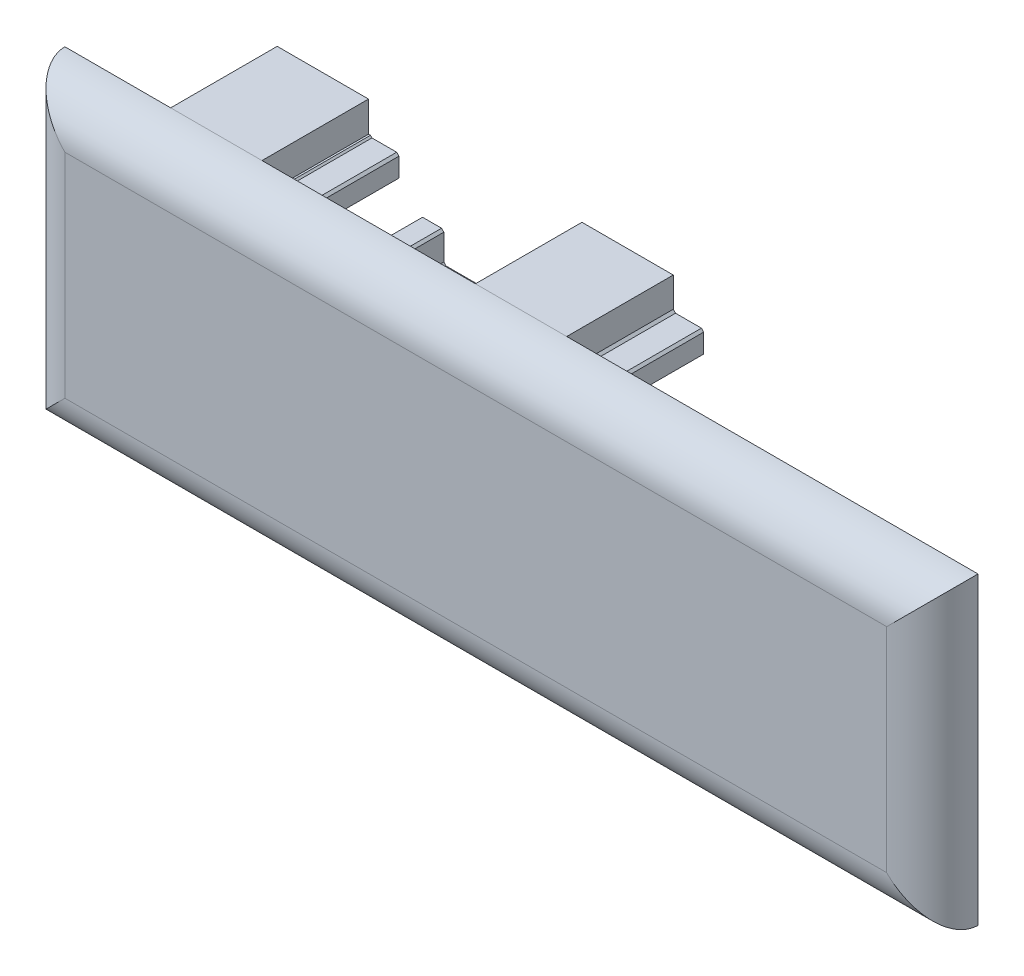
SolidWorks part; units mm, degrees
ref_plane "前视基准面" through (0, 0, 0) normal (0, 0, 1) x (1, 0, 0)
ref_plane "上视基准面" through (0, 0, 0) normal (0, 1, 0) x (1, 0, 0)
ref_plane "右视基准面" through (0, 0, 0) normal (1, 0, 0) x (0, 0, -1)
sketch "草图1" plane through (0, 0, 0) normal (0, 0, 1) x (1, 0, 0)
  line L0 (0, -1000) -> (0, 49000) construction
  line L1 (-3.2, 10) -> (-3.2, 8.5) construction
  line L2 (-10, -10) -> (10, -10) construction
  line L3 (-10, -10) -> (-10, 10) construction
  line L4 (-10, 10) -> (10, 10) construction
  line L5 (-1000, 0) -> (49000, 0) construction
  line L6 (10, -10) -> (10, 10) construction
  line L7 (-10, -10) -> (10, 10) construction
  line L8 (-10, 10) -> (10, -10) construction
  line L9 (-3.2, 8.5) -> (-5.5, 8.5) construction
  line L10 (-5.5, 8.5) -> (-5.5, 6.7) construction
  line L11 (-5.5, 6.7) -> (-2.8, 4) construction
  line L12 (-2.8, 4) -> (2.8, 4) construction
  line L13 (5.5, 6.7) -> (2.8, 4) construction
  line L14 (5.5, 8.5) -> (5.5, 6.7) construction
  line L15 (3.2, 8.5) -> (5.5, 8.5) construction
  line L16 (3.2, 10) -> (3.2, 8.5) construction
  line L17 (8.5, 3.2) -> (8.5, 5.5) construction
  line L18 (8.5, 5.5) -> (6.7, 5.5) construction
  line L19 (6.7, 5.5) -> (4, 2.8) construction
  line L20 (4, 2.8) -> (4, -2.8) construction
  line L21 (6.7, -5.5) -> (4, -2.8) construction
  line L22 (8.5, -5.5) -> (6.7, -5.5) construction
  line L23 (8.5, -3.2) -> (8.5, -5.5) construction
  line L24 (10, 3.2) -> (8.5, 3.2) construction
  line L25 (10, -3.2) -> (8.5, -3.2) construction
  line L26 (3.2, -8.5) -> (5.5, -8.5) construction
  line L27 (5.5, -8.5) -> (5.5, -6.7) construction
  line L28 (5.5, -6.7) -> (2.8, -4) construction
  line L29 (2.8, -4) -> (-2.8, -4) construction
  line L30 (-5.5, -6.7) -> (-2.8, -4) construction
  line L31 (-5.5, -8.5) -> (-5.5, -6.7) construction
  line L32 (-3.2, -8.5) -> (-5.5, -8.5) construction
  line L33 (3.2, -10) -> (3.2, -8.5) construction
  line L34 (-3.2, -10) -> (-3.2, -8.5) construction
  line L35 (-8.5, -3.2) -> (-8.5, -5.5) construction
  line L36 (-8.5, -5.5) -> (-6.7, -5.5) construction
  line L37 (-6.7, -5.5) -> (-4, -2.8) construction
  line L38 (-4, -2.8) -> (-4, 2.8) construction
  line L39 (-6.7, 5.5) -> (-4, 2.8) construction
  line L40 (-8.5, 5.5) -> (-6.7, 5.5) construction
  line L41 (-8.5, 3.2) -> (-8.5, 5.5) construction
  line L42 (-10, -3.2) -> (-8.5, -3.2) construction
  line L43 (-10, 3.2) -> (-8.5, 3.2) construction
  line L44 (-10, 10) -> (-50, 10) construction
  line L45 (-50, 10) -> (-50, -10) construction
  line L46 (-50, -10) -> (-10, -10) construction
  line L47 (-50, -10) -> (21, -10)
  line L48 (-21, 30) -> (21, 30) construction
  line L49 (-21, 30) -> (-21, 44.755)
  line L50 (-16, 72) -> (-6.245, 72)
  line L51 (21, 30) -> (21, 44.755)
  line L52 (-21, 30) -> (21, 72) construction
  line L53 (-21, 72) -> (21, 30) construction
  line L54 (161.103, 104.1617) -> (226.103, 104.1617) construction
  line L55 (161.103, 104.1617) -> (161.103, 51.1617) construction
  line L56 (161.103, 51.1617) -> (226.103, 51.1617) construction
  line L57 (226.103, 104.1617) -> (226.103, 51.1617) construction
  line L58 (21, -10) -> (21, 30)
  line L59 (-21, 13) -> (-50, 13)
  line L60 (-50, 10) -> (10, 10)
  line L61 (-21, 13) -> (-21, 30)
  line L62 (6.245, 72) -> (16, 72)
  line L63 (-21, 57.245) -> (-21, 67)
  line L64 (21, 57.245) -> (21, 67)
  line L65 (-21, 13) -> (10, 13)
  line L66 (10, 13) -> (10, 10)
  line L67 (-50, -10) -> (-50, 10)
  line L68 (-24.525, 6) -> (-15.525, 6)
  line L69 (-50, 13) -> (-50, 10)
  line L70 (-3, 10) -> (-3, 8)
  line L71 (-3, 8) -> (-5, 8)
  line L72 (-5, 8) -> (-5, 6.5)
  line L73 (-5, 6.5) -> (-4.5, 6)
  line L74 (-4.5, 6) -> (4.5, 6)
  line L75 (5, 6.5) -> (4.5, 6)
  line L76 (5, 8) -> (5, 6.5)
  line L77 (3, 10) -> (3, 8)
  line L78 (3, 8) -> (5, 8)
  line L79 (-15.025, 6.5) -> (-15.525, 6)
  line L80 (-15.025, 8) -> (-15.025, 6.5)
  line L81 (-17.025, 8) -> (-15.025, 8)
  line L82 (-17.025, 10) -> (-17.025, 8)
  line L83 (-23.025, 10) -> (-23.025, 8)
  line L84 (-23.025, 8) -> (-25.025, 8)
  line L85 (-25.025, 8) -> (-25.025, 6.5)
  line L86 (-25.025, 6.5) -> (-24.525, 6)
  line L87 (-44.55, 6) -> (-35.55, 6)
  line L88 (-35.05, 6.5) -> (-35.55, 6)
  line L89 (-35.05, 8) -> (-35.05, 6.5)
  line L90 (-37.05, 8) -> (-35.05, 8)
  line L91 (-37.05, 10) -> (-37.05, 8)
  line L92 (-43.05, 10) -> (-43.05, 8)
  line L93 (-43.05, 8) -> (-45.05, 8)
  line L94 (-45.05, 8) -> (-45.05, 6.5)
  line L95 (-45.05, 6.5) -> (-44.55, 6)
  line L96 (-30, 10) -> (-30, -10) construction
  line L97 (-40, 10) -> (-40, -10) construction
  line L98 (-34, 4.55) -> (-34, -4.45)
  line L99 (-33.5, -4.95) -> (-34, -4.45)
  line L100 (-32, -4.95) -> (-33.5, -4.95)
  line L101 (-32, -2.95) -> (-32, -4.95)
  line L102 (-32, 3.05) -> (-28, 3.05)
  line L103 (-28, -2.95) -> (-32, -2.95)
  line L104 (-32, 3.05) -> (-32, 5.05)
  line L105 (-32, 5.05) -> (-33.5, 5.05)
  line L106 (-33.5, 5.05) -> (-34, 4.55)
  line L107 (-35.45, -6) -> (-44.45, -6)
  line L108 (-44.95, -6.5) -> (-44.45, -6)
  line L109 (-44.95, -8) -> (-44.95, -6.5)
  line L110 (-42.95, -8) -> (-44.95, -8)
  line L111 (-42.95, -10) -> (-42.95, -8)
  line L112 (-36.95, -10) -> (-36.95, -8)
  line L113 (-36.95, -8) -> (-34.95, -8)
  line L114 (-34.95, -8) -> (-34.95, -6.5)
  line L115 (-34.95, -6.5) -> (-35.45, -6)
  line L116 (-46, -4.55) -> (-46, 4.45) construction
  line L117 (-46.5, 4.95) -> (-46, 4.45) construction
  line L118 (-48, 4.95) -> (-46.5, 4.95) construction
  line L119 (-48, 2.95) -> (-48, 4.95) construction
  line L120 (-50, 2.95) -> (-48, 2.95) construction
  line L121 (-50, -3.05) -> (-48, -3.05) construction
  line L122 (-48, -3.05) -> (-48, -5.05) construction
  line L123 (-48, -5.05) -> (-46.5, -5.05) construction
  line L124 (-46.5, -5.05) -> (-46, -4.55) construction
  line L125 (-26.5, 5.05) -> (-26, 4.55)
  line L126 (-28, 5.05) -> (-26.5, 5.05)
  line L127 (-28, 3.05) -> (-28, 5.05)
  line L128 (-28, -2.95) -> (-28, -4.95)
  line L129 (-28, -4.95) -> (-26.5, -4.95)
  line L130 (-26.5, -4.95) -> (-26, -4.45)
  line L131 (-26, 4.55) -> (-26, -4.45)
  line L132 (-30, -2.95) -> (-32, -2.95) [skipped]
  line L133 (-30, 3.05) -> (-32, 3.05) [skipped]
  line L134 (-25.025, -6.5) -> (-24.525, -6)
  line L135 (-25.025, -8) -> (-25.025, -6.5)
  line L136 (-23.025, -8) -> (-25.025, -8)
  line L137 (-23.025, -10) -> (-23.025, -8)
  line L138 (-17.025, -10) -> (-17.025, -8)
  line L139 (-17.025, -8) -> (-15.025, -8)
  line L140 (-15.025, -8) -> (-15.025, -6.5)
  line L141 (-15.025, -6.5) -> (-15.525, -6)
  line L142 (-24.525, -6) -> (-15.525, -6)
  line L143 (10, 10) -> (10, -10)
  circle A0 centre (0, 51) radius 11.5
  circle A1 centre (15.5, 66.5) radius 1.7
  circle A2 centre (15.5, 35.5) radius 1.7
  circle A3 centre (-15.5, 35.5) radius 1.7
  circle A4 centre (-15.5, 66.5) radius 1.7
  arc A5 (16, 72) -> (21, 67) centre (16, 67) cw
  arc A6 (-21, 67) -> (-16, 72) centre (-16, 67) cw
  arc A7 (-2.3419, 70.125) -> (2.3419, 70.125) centre (0, 72) ccw
  arc A8 (-2.3419, 70.125) -> (-6.245, 72) centre (-6.245, 67) ccw
  arc A9 (2.3419, 70.125) -> (6.245, 72) centre (6.245, 67) cw
  arc A10 (19.125, 53.3419) -> (19.125, 48.6581) centre (21, 51) ccw
  arc A11 (19.125, 48.6581) -> (21, 44.755) centre (16, 44.755) cw
  arc A12 (19.125, 53.3419) -> (21, 57.245) centre (16, 57.245) ccw
  arc A16 (-19.125, 48.6581) -> (-19.125, 53.3419) centre (-21, 51) ccw
  arc A17 (-19.125, 53.3419) -> (-21, 57.245) centre (-16, 57.245) cw
  arc A18 (-19.125, 48.6581) -> (-21, 44.755) centre (-16, 44.755) ccw
  point P0 (0, 0)
  point P18 (0, 4)
  point P23 (0, 51)
  point P58 (0, 0)
  point P82 (0, 51)
  point P93 (3, 72)
  point P110 (0, 6)
  point P118 (0, 51)
  point P154 (-40, 0)
  point P176 (-40, 0)
  point P188 (-40, 0)
  dimension "D12" = 3
  dimension "D17" = 3.4
  dimension "D20" = 5
  dimension "D21" = 3
  dimension "D22" = 5
  dimension "D23" = 5
  dimension "D1" = 20
  dimension "D2" = 20
  dimension "D3" = 6.4
  dimension "D4" = 1.5
  dimension "D5" = 11
  dimension "D6" = 6
  dimension "D7" = 1.8
  dimension "D9" = 60
  dimension "D10" = 42
  dimension "D11" = 42
  dimension "D13" = 20
  dimension "D14" = 53
  dimension "D15" = 65
  dimension "D16" = 3
  dimension "D19" = 31
  dimension "D26" = 3
  dimension "D27" = 2
  dimension "D28" = 2
  dimension "D29" = 1.5
  dimension "D30" = 2
  dimension "D31" = 4.5
  dimension "D33" = 10
  dimension "D8" = 10
  dimension "D18" = 4
extrude "凸台-拉伸1" add sketch "草图1" along normal blind 3 contours L143 L60 L77 L78 L76 L75 L74 L73 L72 L71 L70 L82 L81 L80 L79 L68 L86 L85 L84 L83 L91 L90 L89 L88 L87 L95 L94 L93 L92 L67 L47 L111 L110 L109 L108 L107 L115 L114 L113 L112 L137 L136 L135 L134 L142 L141 L140 | L85 L86 L68 L79 L80 L81 L82 L60 L83 L84 | L78 L77 L60 L70 L71 L72 L73 L74 L75 L76 | L131 L125 L126 L127 L102 L104 L105 L106 L98 L99 L100 L101 L103 L128 L129 L130 | L94 L95 L87 L88 L89 L90 L91 L60 L92 L93 | L114 L115 L107 L108 L109 L110 L111 L47 L112 L113 | L142 L134 L135 L136 L137 L47 L138 L139 L140 L141 region at (-18.6995, -0.2553, 0) region at (-39.95, -7.7625, 0) region at (-40.05, 7.7625, 0) region at (-20.025, -7.7625, 0) region at (-20.025, 7.7625, 0) region at (0, 7.7625, 0) region at (-30, 0.05, 0)
extrude "凸台-拉伸3" add sketch "草图1<5>" against normal blind 7 contours L85 L86 L68 L79 L80 L81 L82 L60 L83 L84 | L94 L95 L87 L88 L89 L90 L91 L60 L92 L93 | L131 L125 L126 L127 L102 L104 L105 L106 L98 L99 L100 L101 L103 L128 L129 L130 | L142 L134 L135 L136 L137 L47 L138 L139 L140 L141 | L114 L115 L107 L108 L109 L110 L111 L47 L112 L113 region at (-39.95, -7.7625, 0) region at (-40.05, 7.7625, 0) region at (-20.025, -7.7625, 0) region at (-20.025, 7.7625, 0) region at (-30, 0.05, 0)
sketch "草图1<5>" plane through (0, 0, 0) normal (0, 0, 1) x (1, 0, 0) same geometry as "草图1"
sketch "草图5" plane through (0, 0, -7) normal (0, 0, -1) x (-1, 0, 0)
  line L0 (17.025, 10) -> (17.025, 8) construction
  line L1 (15.025, 8) -> (17.025, 8)
  line L2 (15.025, 8) -> (15.025, 7.9)
  line L3 (15.025, 7.9) -> (17.025, 7.9)
  line L4 (17.025, 8) -> (17.025, 7.9)
  line L5 (-1000, 0) -> (49000, 0) construction
  line L6 (30, -996.95) -> (30, 49003.05) construction
  line L7 (32, 3.05) -> (28, 3.05) construction
  line L8 (20.025, -993.9) -> (20.025, 49006.1) construction
  line L9 (24.525, 6) -> (15.525, 6) construction
  line L10 (40.05, -993.9) -> (40.05, 49006.1) construction
  line L11 (44.55, 6) -> (35.55, 6) construction
  line L12 (23.025, 8) -> (23.025, 7.9)
  line L13 (25.025, 7.9) -> (23.025, 7.9)
  line L14 (25.025, 8) -> (25.025, 7.9)
  line L15 (25.025, 8) -> (23.025, 8)
  line L16 (34.975, 8) -> (36.975, 8)
  line L17 (34.975, 8) -> (34.975, 7.9)
  line L18 (34.975, 7.9) -> (36.975, 7.9)
  line L19 (36.975, 8) -> (36.975, 7.9)
  line L20 (42.975, 8) -> (42.975, 7.9)
  line L21 (44.975, 7.9) -> (42.975, 7.9)
  line L22 (44.975, 8) -> (44.975, 7.9)
  line L23 (44.975, 8) -> (42.975, 8)
  line L24 (28, 5.05) -> (26.5, 5.05) construction
  line L25 (27.9, 5.05) -> (32.1, 5.05)
  line L26 (27.9, 5.05) -> (27.9, 3.05)
  line L27 (27.9, 3.05) -> (32.1, 3.05)
  line L28 (32.1, 5.05) -> (32.1, 3.05)
  line L30 (32, 3.05) -> (32, 5.05) construction
  line L31 (32.1, -5.05) -> (32.1, -3.05)
  line L32 (27.9, -3.05) -> (32.1, -3.05)
  line L33 (27.9, -5.05) -> (27.9, -3.05)
  line L34 (27.9, -5.05) -> (32.1, -5.05)
  point P15 (30, 3.05)
  point P20 (20.025, 6)
  point P25 (40.05, 6)
  dimension "D1" = 0.1
  dimension "D2" = 0.1
extrude "切除-拉伸2" cut sketch "草图5" against normal up to surface (7 mm away) up to face at (-29.6477, 0.0455, 0)
chamfer "倒角1" distance 0.15 angle 45 23 edges at (-32.1, -3.05, -3.5) (-32.1, -4.95, -3.5) (-27.9, -3.05, -3.5) (-27.9, -4.95, -3.5) (-32.1, 5.05, -3.5) (-32.1, 3.05, -3.5) (-27.9, 5.05, -3.5) (-27.9, 3.05, -3.5) (-42.975, 7.9, -3.5) (-25.025, 7.9, -3.5) (-23.025, 7.9, -3.5) (-35.05, 7.9, -3.5) (-36.975, 7.9, -3.5) (-15.025, 7.9, -3.5) (-17.025, 7.9, -3.5) (-34.95, -8, -3.5) (-36.95, -8, -3.5) (-44.95, -8, -3.5) (-42.95, -8, -3.5) (-15.025, -8, -3.5) (-17.025, -8, -3.5) (-25.025, -8, -3.5) (-23.025, -8, -3.5)
sketch "草图6" plane through (0, 0, 0) normal (0, 0, -1) x (-1, 0, 0)
  line L0 (15.025, 10) -> (15.025, -10)
  line L1 (17.025, 10) -> (-10, 10) construction
  line L2 (17.025, -10) -> (-10, -10) construction
  line L3 (15.025, -10) -> (45.05, -10)
  line L4 (50, -10) -> (42.95, -10) construction
  line L5 (45.05, -10) -> (45.05, 10)
  line L6 (50, 10) -> (43.05, 10) construction
  line L7 (45.05, 10) -> (15.025, 10)
  line L8 (45.05, 8) -> (45.05, 6.5) construction
  line L9 (15.025, 7.75) -> (15.025, 6.5) construction
extrude "切除-拉伸3" [suppressed] cut sketch "草图6" against normal through all flip side to cut
fillet "圆角1" radius 3 4 edges at (10, 0, 3) (-20, -10, 3) (-20, 10, 3) (-50, 0, 3)
